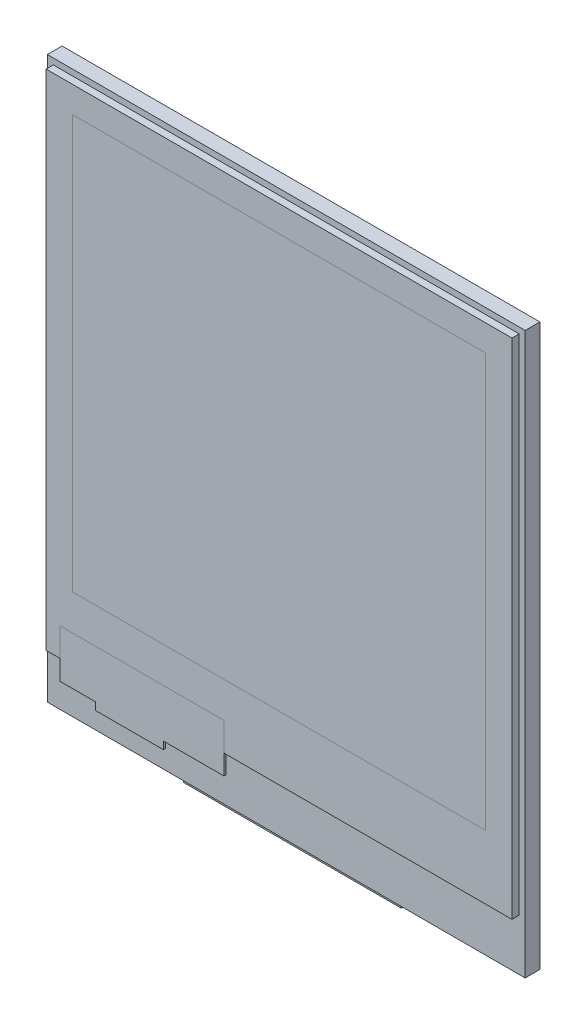
SolidWorks part; units mm, degrees
ref_plane "前视基准面" through (0, 0, 0) normal (0, 0, 1) x (1, 0, 0)
ref_plane "上视基准面" through (0, 0, 0) normal (0, 1, 0) x (1, 0, 0)
ref_plane "右视基准面" through (0, 0, 0) normal (1, 0, 0) x (0, 0, -1)
sketch "草图1" plane through (0, 0, 0) normal (0, 0, 1) x (1, 0, 0)
  line L1 (15.9, -18.66) -> (-15.9, -18.66)
  line L2 (15.9, -18.66) -> (15.9, 18.66)
  line L3 (15.9, 18.66) -> (-15.9, 18.66)
  line L4 (-15.9, -18.66) -> (-15.9, 18.66)
  line L5 (15.9, -18.66) -> (-15.9, 18.66) construction
  line L6 (15.9, 18.66) -> (-15.9, -18.66) construction
  point P0 (0, 0)
  dimension "D1" = 31.8
  dimension "D2" = 37.32
extrude "凸台-拉伸1" add sketch "草图1" along normal blind 0.98
sketch "草图2" plane through (0, 0, 0.98) normal (0, 0, 1) x (1, 0, 0)
  line L0 (0, 18.26) -> (0, 0) construction
  line L1 (-15.5, 18.26) -> (15.5, 18.26)
  line L2 (-15.5, 18.26) -> (-15.5, -15.24)
  line L3 (-15.5, -15.24) -> (15.5, -15.24)
  line L4 (15.5, 18.26) -> (15.5, -15.24)
  line L5 (15.9, 18.66) -> (-15.9, 18.66) construction
  dimension "D1" = 31
  dimension "D2" = 33.5
  dimension "D3" = 0.4
extrude "凸台-拉伸2" add sketch "草图2" along normal blind 1.46 from surface starting at face at (0, 0, 0)
sketch "草图5" plane through (0, 0, 1.46) normal (0, 0, 1) x (1, 0, 0)
  line L0 (-14.57, -15.24) -> (-14.57, -16.56)
  line L1 (-15.5, -15.24) -> (15.5, -15.24) construction
  line L2 (-14.57, -16.56) -> (-12.2, -16.56)
  line L3 (-12.2, -16.56) -> (-12.2, -17.06)
  line L4 (-12.2, -17.06) -> (-7.7, -17.06)
  line L5 (-7.7, -17.06) -> (-7.7, -16.56)
  line L6 (-7.7, -16.56) -> (-3.67, -16.56)
  line L7 (-3.67, -16.56) -> (-3.67, -15.24)
  line L8 (15.5, -15.24) -> (-15.5, -15.24) construction
  line L9 (-3.67, -15.24) -> (-14.57, -15.24)
  line L10 (-15.9, 18.66) -> (-15.9, -18.66) construction
  line L11 (-15.9, -18.66) -> (15.9, -18.66) construction
  point P7 (-14.57, -15.9)
  dimension "D1" = 10.9
  dimension "D2" = 1.33
  dimension "D3" = 3.7
  dimension "D4" = 4.5
  dimension "D5" = 2.1
  dimension "D6" = 0.5
extrude "凸台-拉伸3" add sketch "草图5" against normal blind 0.15
sketch "草图6" plane through (0, 0, 0.98) normal (0, 0, 1) x (1, 0, 0)
  line L0 (-15.9, -18.66) -> (15.9, -18.66) construction
  line L1 (-7.25, -18.66) -> (7.25, -18.66)
  line L2 (-7.25, -18.66) -> (-7.25, -19.16)
  line L3 (-7.25, -19.16) -> (7.25, -19.16)
  line L4 (7.25, -18.66) -> (7.25, -19.16)
  line L5 (0, 0) -> (0, -18.66) construction
  dimension "D1" = 14.5
  dimension "D2" = 0.5
extrude "凸台-拉伸4" add sketch "草图6" against normal blind 0.15 from offset 0.4 offset against normal yes
sketch "草图7" plane through (0, 0, 1.46) normal (0, 0, 1) x (1, 0, 0)
  line L0 (0, 2.765) -> (0, 0) construction
  line L1 (13.755, -10.99) -> (-13.755, -10.99)
  line L2 (13.755, -10.99) -> (13.755, 16.52)
  line L3 (13.755, 16.52) -> (-13.755, 16.52)
  line L4 (-13.755, -10.99) -> (-13.755, 16.52)
  line L5 (13.755, -10.99) -> (-13.755, 16.52) construction
  line L6 (13.755, 16.52) -> (-13.755, -10.99) construction
  line L7 (15.9, 18.66) -> (-15.9, 18.66) construction
  point P0 (0, 2.765)
  dimension "D1" = 27.51
  dimension "D2" = 2.14
wrap "包覆1" sketch "草图7" wrap type scribe source sketch "草图7"
sketch "草图9" plane through (0, 0, 1.46) normal (0, 0, 1) x (1, 0, 0)
  line L0 (-14.57, -15.24) -> (-14.57, -13.36)
  line L1 (-14.57, -13.36) -> (-3.67, -13.36)
  line L2 (-3.67, -13.36) -> (-3.67, -15.24)
  line L3 (-3.67, -16.56) -> (-3.67, -15.24) construction
  line L4 (-7.7, -16.56) -> (-3.67, -16.56) construction
  line L5 (-7.7, -17.06) -> (-7.7, -16.56) construction
  line L6 (-12.2, -17.06) -> (-7.7, -17.06) construction
  line L7 (-12.2, -16.56) -> (-12.2, -17.06) construction
  line L8 (-14.57, -16.56) -> (-12.2, -16.56) construction
  line L9 (-14.57, -15.24) -> (-14.57, -16.56) construction
  line L10 (-3.67, -16.56) -> (-3.67, -15.24)
  line L11 (-7.7, -16.56) -> (-3.67, -16.56)
  line L12 (-7.7, -17.06) -> (-7.7, -16.56)
  line L13 (-12.2, -17.06) -> (-7.7, -17.06)
  line L14 (-12.2, -16.56) -> (-12.2, -17.06)
  line L15 (-14.57, -16.56) -> (-12.2, -16.56)
  line L16 (-14.57, -15.24) -> (-14.57, -16.56)
  dimension "D1" = 3.2
wrap "包覆2" sketch "草图9" wrap type scribe source sketch "草图9"
